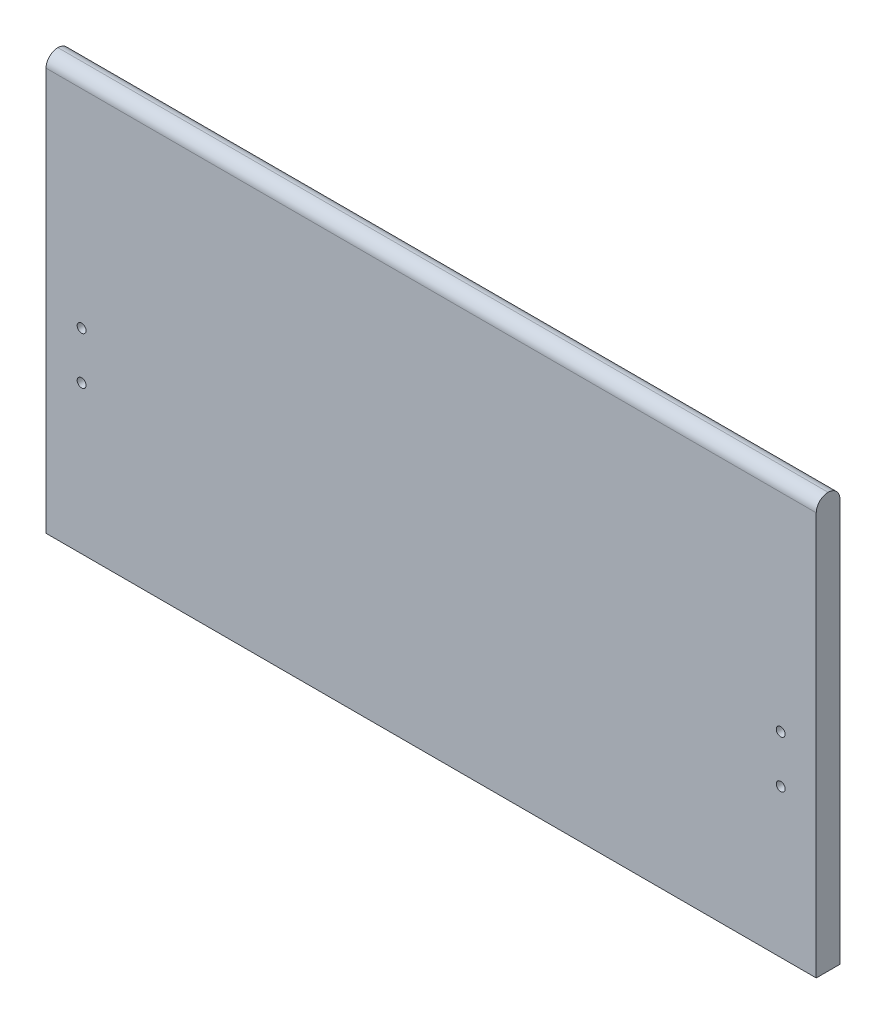
SolidWorks part; units mm, degrees
material "Faggio"
ref_plane "Piano frontale" through (0, 0, 0) normal (0, 0, 1) x (1, 0, 0)
ref_plane "Piano superiore" through (0, 0, 0) normal (0, 1, 0) x (1, 0, 0)
ref_plane "Piano destro" through (0, 0, 0) normal (1, 0, 0) x (0, 0, -1)
sketch "Schizzo1" plane through (0, 0, 0) normal (0, 0, 1) x (1, 0, 0)
  line L1 (0, 0) -> (1300, 0)
  line L2 (0, 0) -> (0, -700)
  line L3 (0, -700) -> (1300, -700)
  line L4 (1300, 0) -> (1300, -700)
  dimension "D1" = 1300
  dimension "D2" = 700
extrude "Estrusione-Estrusione1" add sketch "Schizzo1" along normal blind 40
fillet "Raccordo1" radius 20 2 edges at (650, 0, 0) (650, 0, 40)
sketch "Schizzo2" plane through (0, 0, 40) normal (0, 0, 1) x (1, 0, 0)
  line L0 (1300, -700) -> (1300, -20) construction
  line L1 (0, -20) -> (0, -700) construction
  line L2 (0, -700) -> (1300, -700) construction
  circle A0 centre (60, -370) radius 7.5
  circle A1 centre (60, -450) radius 7.5
  circle A2 centre (1240, -370) radius 7.5
  circle A3 centre (1240, -450) radius 7.5
  dimension "D1" = 15
  dimension "D2" = 15
  dimension "D3" = 15
  dimension "D4" = 15
  dimension "D5" = 80
  dimension "D6" = 80
  dimension "D7" = 60
  dimension "D8" = 60
  dimension "D9" = 250
  dimension "D10" = 250
extrude "Taglio-Estrusione1" cut sketch "Schizzo2" against normal blind 30
